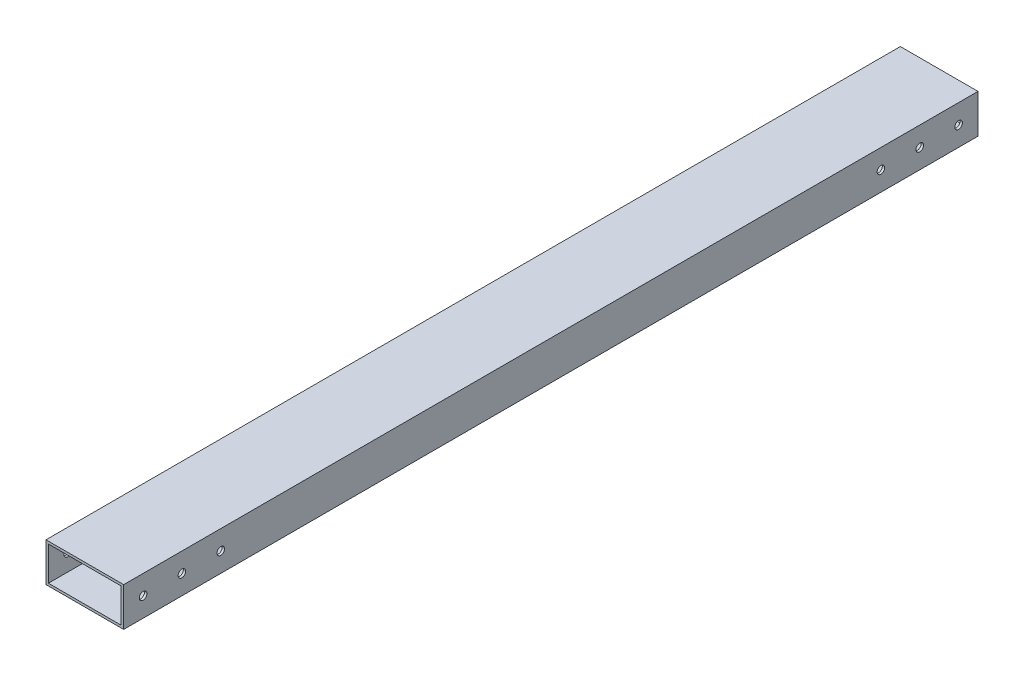
SolidWorks part; units mm, degrees
ref_plane "Front Plane" through (0, 0, 0) normal (0, 0, 1) x (1, 0, 0)
ref_plane "Top Plane" through (0, 0, 0) normal (0, 1, 0) x (1, 0, 0)
ref_plane "Right Plane" through (0, 0, 0) normal (1, 0, 0) x (0, 0, -1)
sketch "Sketch1" plane through (0, 0, 0) normal (0, 0, 1) x (1, 0, 0)
  line L1 (-25.4, -12.7) -> (25.4, -12.7)
  line L2 (-25.4, -12.7) -> (-25.4, 12.7)
  line L3 (-25.4, 12.7) -> (25.4, 12.7)
  line L4 (25.4, -12.7) -> (25.4, 12.7)
  line L5 (-25.4, -12.7) -> (25.4, 12.7) construction
  line L6 (-25.4, 12.7) -> (25.4, -12.7) construction
  point P0 (0, 0)
  dimension "D1" = 50.8
  dimension "D2" = 25.4
extrude "Boss-Extrude1" add sketch "Sketch1" along normal mid plane 558.8
shell "Shell1" thickness 1.5875 removed face at (0, 0, -279.4) removed face at (0, 0, 279.4)
sketch "Sketch3" plane through (0, 0, 0) normal (1, 0, 0) x (0, 0, -1)
  line L0 (-279.4, -12.7) -> (-279.4, 12.7) construction
  line L1 (0, 12.7) -> (0, -12.7) construction
  line L2 (-279.4, 12.7) -> (279.4, 12.7) construction
  line L3 (-279.4, -12.7) -> (279.4, -12.7) construction
  circle A0 centre (-266.7, 0) radius 2.4892
  circle A1 centre (-241.3, 0) radius 2.4892
  circle A2 centre (-215.9, 0) radius 2.4892
  circle A3 centre (215.9, 0) radius 2.4892
  circle A4 centre (241.3, 0) radius 2.4892
  circle A5 centre (266.7, 0) radius 2.4892
  point P21 (0, 0)
  dimension "D2" = 4.9784
  dimension "D1" = 12.7
  dimension "D3" = 25.4
  dimension "D4" = 25.4
  dimension "D5" = 12.7
extrude "Cut-Extrude1" cut sketch "Sketch3" against normal through all both and the other way through all
equation "\"D4@Sketch3\"=\"D3@Sketch3\""
